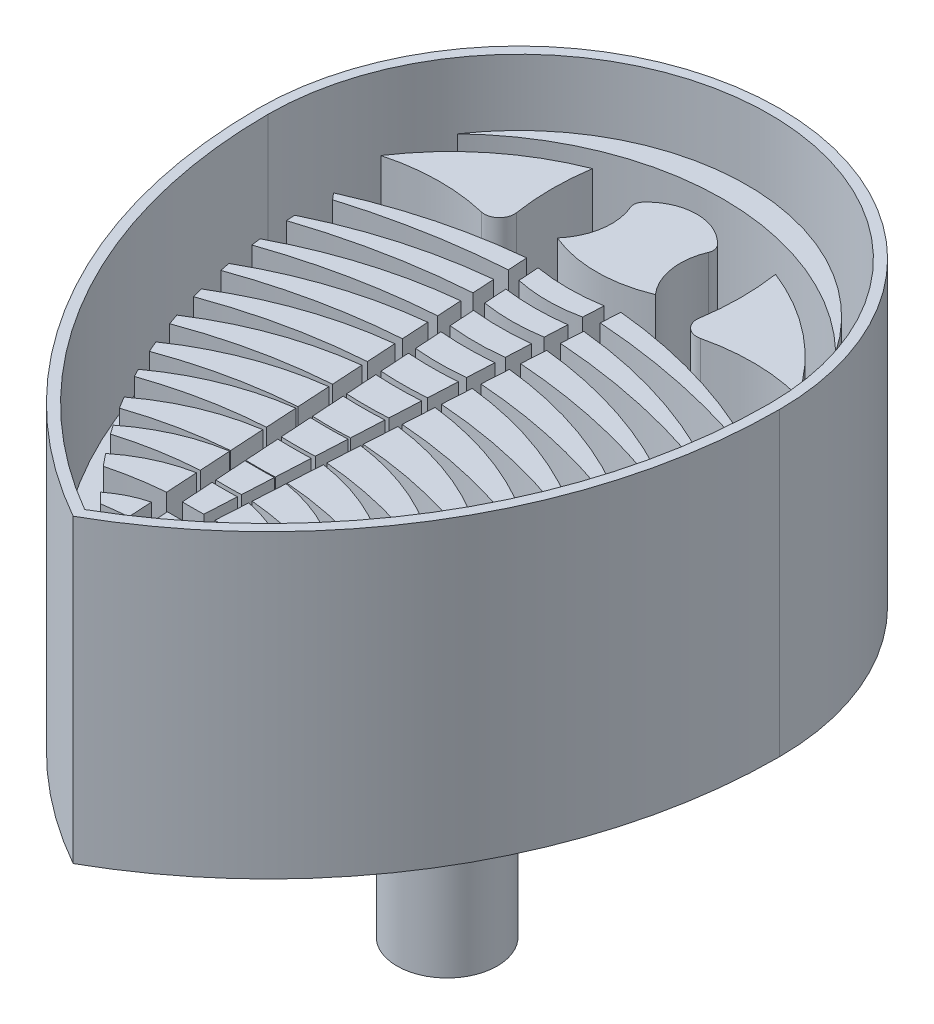
SolidWorks part; units mm, degrees
ref_plane "Přední rovina" through (0, 0, 0) normal (0, 0, 1) x (1, 0, 0)
ref_plane "Horní rovina" through (0, 0, 0) normal (0, 1, 0) x (1, 0, 0)
ref_plane "Pravá rovina" through (0, 0, 0) normal (1, 0, 0) x (0, 0, -1)
sketch "Skica1" plane through (0, 0, 0) normal (0, 1, 0) x (1, 0, 0)
  arc A0 (5, 0) -> (-5, 0) centre (0, 0) ccw
  arc A1 (-5, 0) -> (0, -8.6603) centre (5, 0) ccw
  arc A2 (0, -8.6603) -> (5, 0) centre (-5, 0) ccw
  dimension "D1" = 10
extrude "Přidat vysunutím1" add sketch "Skica1" against normal blind 3
sketch "Skica2" plane through (0, 0, 0) normal (0, 1, 0) x (1, 0, 0)
  line L0 (-0.9396, 1.0946) -> (-0.9163, 0.7054)
  line L1 (0.9396, 1.0946) -> (0.9163, 0.7054)
  line L2 (-0.4639, -6.8657) -> (-0.435, -7.3481)
  line L3 (-0.521, -5.9092) -> (-0.4831, -6.5437)
  line L4 (0.521, -5.9092) -> (0.4831, -6.5437)
  line L5 (-0.5631, -5.2058) -> (-0.5258, -5.8294)
  line L6 (-0.605, -4.5041) -> (-0.5642, -5.1865)
  line L7 (0.605, -4.5041) -> (0.5642, -5.1865)
  line L8 (0.6469, -3.8031) -> (0.6088, -4.4409)
  line L9 (-0.6469, -3.8031) -> (-0.6097, -4.4257)
  line L10 (-0.6887, -3.1028) -> (-0.6498, -3.7549)
  line L11 (0.6887, -3.1028) -> (0.6498, -3.7549)
  line L12 (0.7306, -2.4028) -> (0.6935, -3.0231)
  line L13 (-0.7306, -2.4028) -> (-0.6935, -3.0231)
  line L14 (-0.7724, -1.703) -> (-0.7376, -2.2844)
  line L15 (0.7724, -1.703) -> (0.7376, -2.2844)
  line L16 (0.8142, -1.0034) -> (0.7821, -1.5408)
  line L17 (-0.8142, -1.0034) -> (-0.7821, -1.5408)
  line L18 (-0.856, -0.304) -> (-0.8267, -0.7938)
  line L19 (0.856, -0.304) -> (0.8267, -0.7938)
  line L20 (0.8978, 0.3954) -> (0.8715, -0.0448)
  line L21 (-0.8978, 0.3954) -> (-0.8715, -0.0448)
  line L22 (0.4639, -6.8657) -> (0.434, -7.3648)
  line L23 (0.5631, -5.2058) -> (0.5249, -5.8452)
  line L24 (-0.6539, 1.0367) -> (-0.6272, 0.6279)
  line L25 (0.6621, 1.0381) -> (0.641, 0.6309)
  line L26 (-0.6089, 0.3483) -> (-0.5795, -0.1033)
  line L27 (0.6264, 0.3507) -> (0.6031, -0.0994)
  line L28 (0.5906, -0.3401) -> (0.5649, -0.8356)
  line L29 (-0.5638, -0.3429) -> (-0.5314, -0.8398)
  line L30 (0.5547, -1.0329) -> (0.5266, -1.5735)
  line L31 (-0.5186, -1.0361) -> (-0.4832, -1.5778)
  line L32 (-0.4732, -1.7307) -> (-0.4351, -2.3147)
  line L33 (0.5186, -1.7274) -> (0.4884, -2.3105)
  line L34 (-0.4279, -2.4264) -> (-0.3873, -3.0482)
  line L35 (0.4826, -2.4231) -> (0.4504, -3.0442)
  line L36 (-0.3369, -3.8204) -> (-0.2962, -4.4435)
  line L37 (0.4103, -3.8173) -> (0.378, -4.4401)
  line L38 (0.4464, -3.1197) -> (0.4126, -3.7721)
  line L39 (-0.3824, -3.123) -> (-0.3398, -3.7759)
  line L40 (0.3377, -5.2158) -> (0.3054, -5.8391)
  line L41 (-0.2456, -5.2184) -> (-0.205, -5.8419)
  line L42 (0.374, -4.5159) -> (0.3387, -5.1981)
  line L43 (-0.2913, -4.5188) -> (-0.2468, -5.2012)
  line L44 (-0.1999, -5.9198) -> (-0.1585, -6.554)
  line L45 (0.3013, -5.9174) -> (0.2685, -6.5517)
  line L46 (-0.1376, -6.874) -> (-0.1061, -7.3562)
  line L47 (0.2518, -6.8721) -> (0.2268, -7.3544)
  arc A0 (3.7723, 2.5471) -> (-3.7723, 2.5471) centre (0, 0) ccw
  arc A1 (3.7723, 2.5471) -> (-3.7723, 2.5471) centre (0, -1.3616) ccw
  arc A2 (-1.826, 3.293) -> (-4.1627, 1.4083) centre (0, -1.3616) ccw
  arc A7 (4.1627, 1.4083) -> (2.1882, 1.4375) centre (3.118, -2.4529) ccw
  arc A8 (-1.826, 3.293) -> (-1.8221, 1.7756) centre (3.118, 2.5471) ccw
  arc A9 (4.1627, 1.4083) -> (1.826, 3.293) centre (0, -1.3616) ccw
  arc A10 (1.8221, 1.7756) -> (1.826, 3.293) centre (-3.118, 2.5471) ccw
  arc A11 (-2.1882, 1.4375) -> (-1.8221, 1.7756) centre (-2.1185, 1.7293) ccw
  arc A12 (1.8221, 1.7756) -> (2.1882, 1.4375) centre (2.1185, 1.7293) ccw
  arc A13 (-2.1882, 1.4375) -> (-4.1627, 1.4083) centre (-3.118, -2.4529) ccw
  arc A15 (-0.9784, 1.7445) -> (-0.778, 3.0046) centre (-1.8819, 2.5341) ccw
  arc A16 (0.778, 3.0046) -> (0.9784, 1.7445) centre (1.8819, 2.5341) ccw
  arc A17 (-0.7425, 3.2169) -> (-0.778, 3.0046) centre (-0.594, 3.083) ccw
  arc A18 (0.778, 3.0046) -> (0.7425, 3.2169) centre (0.594, 3.083) ccw
  arc A20 (3.996, 0.288) -> (0.9396, 1.0946) centre (0, -8.6603) ccw
  arc A21 (-0.9784, 1.7445) -> (0.9784, 1.7445) centre (0, 4.0705) ccw
  arc A22 (0.7425, 3.2169) -> (-0.7425, 3.2169) centre (0, 2.5471) ccw
  arc A23 (3.989, -0.4811) -> (0.8978, 0.3954) centre (0, -8.6603) ccw
  arc A24 (3.9271, -1.2348) -> (0.856, -0.304) centre (0, -8.6603) ccw
  arc A25 (3.8134, -1.9708) -> (0.8142, -1.0034) centre (0, -8.6603) ccw
  arc A26 (3.6503, -2.6874) -> (0.7724, -1.703) centre (0, -8.6603) ccw
  arc A27 (3.4403, -3.3825) -> (0.7306, -2.4028) centre (0, -8.6603) ccw
  arc A28 (3.1856, -4.0546) -> (0.6887, -3.1028) centre (0, -8.6603) ccw
  arc A29 (2.8883, -4.702) -> (0.6469, -3.8031) centre (0, -8.6603) ccw
  arc A30 (2.5505, -5.3234) -> (0.605, -4.5041) centre (0, -8.6603) ccw
  arc A31 (2.1739, -5.9172) -> (0.5631, -5.2058) centre (0, -8.6603) ccw
  arc A32 (1.76, -6.4825) -> (0.521, -5.9092) centre (0, -8.6603) ccw
  arc A33 (1.1422, -7.2005) -> (0.4639, -6.8657) centre (0, -8.6603) ccw
  arc A34 (-4.9974, -0.2302) -> (0, -8.6603) centre (5, 0) ccw
  arc A35 (0, -8.6603) -> (4.9974, -0.2302) centre (-5, 0) ccw
  arc A36 (3.9992, 0.1259) -> (0.9163, 0.7054) centre (0, -12.6603) ccw
  arc A37 (3.9794, -0.6572) -> (0.8715, -0.0448) centre (0, -12.6603) ccw
  arc A38 (3.903, -1.4236) -> (0.8267, -0.7938) centre (0, -12.6603) ccw
  arc A39 (3.773, -2.1713) -> (0.7821, -1.5408) centre (0, -12.6603) ccw
  arc A40 (3.5921, -2.8981) -> (0.7376, -2.2844) centre (0, -12.6603) ccw
  arc A41 (3.3628, -3.6022) -> (0.6935, -3.0231) centre (0, -12.6603) ccw
  arc A42 (3.0872, -4.2819) -> (0.6498, -3.7549) centre (0, -12.6603) ccw
  arc A43 (2.7721, -4.9273) -> (0.6088, -4.4409) centre (-0.103, -12.6603) ccw
  arc A44 (2.4059, -5.5618) -> (0.5642, -5.1865) centre (0, -12.6603) ccw
  arc A45 (2.01, -6.1506) -> (0.5249, -5.8452) centre (-0.103, -12.6603) ccw
  arc A46 (1.5622, -6.7269) -> (0.4831, -6.5437) centre (0, -12.6603) ccw
  arc A47 (0.9136, -7.4357) -> (0.434, -7.3648) centre (-0.103, -12.6603) ccw
  arc A51 (0.9136, -7.4357) -> (1.1422, -7.2005) centre (-6.5, 0) ccw
  arc A52 (-0.9396, 1.0946) -> (-3.996, 0.288) centre (0, -8.6603) ccw
  arc A53 (-1.1422, -7.2005) -> (-0.9445, -7.4046) centre (6.5, 0) ccw
  arc A54 (-1.76, -6.4825) -> (-1.5622, -6.7269) centre (6.5, 0) ccw
  arc A55 (-2.1739, -5.9172) -> (-2.0475, -6.0984) centre (6.5, 0) ccw
  arc A56 (-2.5505, -5.3234) -> (-2.4059, -5.5618) centre (6.5, 0) ccw
  arc A57 (-2.8883, -4.702) -> (-2.8049, -4.8651) centre (6.5, 0) ccw
  arc A58 (-3.1856, -4.0546) -> (-3.0872, -4.2819) centre (6.5, 0) ccw
  arc A59 (-3.4403, -3.3825) -> (-3.3628, -3.6022) centre (6.5, 0) ccw
  arc A60 (-3.6503, -2.6874) -> (-3.5921, -2.8981) centre (6.5, 0) ccw
  arc A61 (-3.8134, -1.9708) -> (-3.773, -2.1713) centre (6.5, 0) ccw
  arc A62 (-3.9271, -1.2348) -> (-3.903, -1.4236) centre (6.5, 0) ccw
  arc A63 (-3.989, -0.4811) -> (-3.9794, -0.6572) centre (6.5, 0) ccw
  arc A64 (3.9992, 0.1259) -> (3.996, 0.288) centre (-6.5, 0) ccw
  arc A65 (3.9794, -0.6572) -> (3.989, -0.4811) centre (-6.5, 0) ccw
  arc A66 (3.903, -1.4236) -> (3.9271, -1.2348) centre (-6.5, 0) ccw
  arc A67 (3.773, -2.1713) -> (3.8134, -1.9708) centre (-6.5, 0) ccw
  arc A68 (3.5921, -2.8981) -> (3.6503, -2.6874) centre (-6.5, 0) ccw
  arc A69 (3.3628, -3.6022) -> (3.4403, -3.3825) centre (-6.5, 0) ccw
  arc A70 (3.0872, -4.2819) -> (3.1856, -4.0546) centre (-6.5, 0) ccw
  arc A71 (2.7721, -4.9273) -> (2.8883, -4.702) centre (-6.5, 0) ccw
  arc A72 (2.4059, -5.5618) -> (2.5505, -5.3234) centre (-6.5, 0) ccw
  arc A73 (2.01, -6.1506) -> (2.1739, -5.9172) centre (-6.5, 0) ccw
  arc A74 (1.5622, -6.7269) -> (1.76, -6.4825) centre (-6.5, 0) ccw
  arc A75 (-0.9163, 0.7054) -> (-3.9992, 0.1259) centre (0, -12.6603) ccw
  arc A76 (-0.8978, 0.3954) -> (-3.989, -0.4811) centre (0, -8.6603) ccw
  arc A77 (-0.8715, -0.0448) -> (-3.9794, -0.6572) centre (0, -12.6603) ccw
  arc A78 (-0.856, -0.304) -> (-3.9271, -1.2348) centre (0, -8.6603) ccw
  arc A79 (-0.8267, -0.7938) -> (-3.903, -1.4236) centre (0, -12.6603) ccw
  arc A80 (-0.8142, -1.0034) -> (-3.8134, -1.9708) centre (0, -8.6603) ccw
  arc A81 (-0.7821, -1.5408) -> (-3.773, -2.1713) centre (0, -12.6603) ccw
  arc A82 (-0.7724, -1.703) -> (-3.6503, -2.6874) centre (0, -8.6603) ccw
  arc A83 (-0.7376, -2.2844) -> (-3.5921, -2.8981) centre (0, -12.6603) ccw
  arc A84 (-0.7306, -2.4028) -> (-3.4403, -3.3825) centre (0, -8.6603) ccw
  arc A85 (-0.6935, -3.0231) -> (-3.3628, -3.6022) centre (0, -12.6603) ccw
  arc A86 (-0.6887, -3.1028) -> (-3.1856, -4.0546) centre (0, -8.6603) ccw
  arc A87 (-0.6498, -3.7549) -> (-3.0872, -4.2819) centre (0, -12.6603) ccw
  arc A88 (-0.6469, -3.8031) -> (-2.8883, -4.702) centre (0, -8.6603) ccw
  arc A89 (-0.6097, -4.4257) -> (-2.8049, -4.8651) centre (-0.103, -12.6603) ccw
  arc A90 (-0.605, -4.5041) -> (-2.5505, -5.3234) centre (0, -8.6603) ccw
  arc A91 (-0.5642, -5.1865) -> (-2.4059, -5.5618) centre (0, -12.6603) ccw
  arc A92 (-0.5631, -5.2058) -> (-2.1739, -5.9172) centre (0, -8.6603) ccw
  arc A93 (-0.5258, -5.8294) -> (-2.0475, -6.0984) centre (-0.103, -12.6603) ccw
  arc A94 (-0.521, -5.9092) -> (-1.76, -6.4825) centre (0, -8.6603) ccw
  arc A95 (-0.4831, -6.5437) -> (-1.5622, -6.7269) centre (0, -12.6603) ccw
  arc A96 (-0.4639, -6.8657) -> (-1.1422, -7.2005) centre (0, -8.6603) ccw
  arc A97 (-0.435, -7.3481) -> (-0.9445, -7.4046) centre (-0.103, -12.6603) ccw
  arc A98 (-3.996, 0.288) -> (-3.9992, 0.1259) centre (6.5, 0) ccw
  arc A100 (5, 0) -> (-5, 0) centre (0, 0) ccw construction
  arc A108 (-0.2913, -4.5188) -> (0.374, -4.5159) centre (0, 5) ccw
  arc A111 (-0.1376, -6.874) -> (0.2518, -6.8721) centre (0, 5) ccw
  arc A112 (-0.6539, 1.0367) -> (0.6621, 1.0381) centre (0, 5) ccw
  arc A113 (-0.5186, -1.0361) -> (0.5547, -1.0329) centre (0, 5) ccw
  arc A114 (-0.4732, -1.7307) -> (0.5186, -1.7274) centre (0, 5) ccw
  arc A115 (-0.5795, -0.1033) -> (0.6031, -0.0994) centre (0, 3.5471) ccw
  arc A116 (-0.6089, 0.3483) -> (0.6264, 0.3507) centre (0, 5) ccw
  arc A117 (-0.5638, -0.3429) -> (0.5906, -0.3401) centre (0, 5) ccw
  arc A118 (-0.4279, -2.4264) -> (0.4826, -2.4231) centre (0, 5) ccw
  arc A119 (-0.4351, -2.3147) -> (0.4884, -2.3105) centre (0, 3.5471) ccw
  arc A120 (-0.3873, -3.0482) -> (0.4504, -3.0442) centre (0, 3.5471) ccw
  arc A121 (-0.3824, -3.123) -> (0.4464, -3.1197) centre (0, 5) ccw
  arc A122 (-0.3369, -3.8204) -> (0.4103, -3.8173) centre (0, 5) ccw
  arc A123 (-0.1999, -5.9198) -> (0.3013, -5.9174) centre (0, 5) ccw
  arc A124 (-0.2456, -5.2184) -> (0.3377, -5.2158) centre (0, 5) ccw
  arc A125 (-0.1585, -6.554) -> (0.2685, -6.5517) centre (0, 3.5471) ccw
  arc A129 (-3.9876, 0.2918) -> (-3.8789, 0.163) centre (0, 3.5471) ccw
  arc A134 (-0.2468, -5.2012) -> (0.3387, -5.1981) centre (0, 3.5471) ccw
  arc A138 (-0.6272, 0.6279) -> (0.641, 0.6309) centre (0, 3.5471) ccw
  arc A139 (-0.4832, -1.5778) -> (0.5266, -1.5735) centre (0, 3.5471) ccw
  arc A140 (-0.2962, -4.4435) -> (0.378, -4.4401) centre (0, 3.5471) ccw
  arc A141 (-0.5314, -0.8398) -> (0.5649, -0.8356) centre (0, 3.5471) ccw
  arc A142 (-0.3398, -3.7759) -> (0.4126, -3.7721) centre (0, 3.5471) ccw
  arc A143 (-0.205, -5.8419) -> (0.3054, -5.8391) centre (0, 3.5471) ccw
  arc A144 (-0.1061, -7.3562) -> (0.2268, -7.3544) centre (0, 3.5471) ccw
  point P44 (0, -12.6603)
  dimension "D1" = 4
  dimension "D4" = 1.5
  dimension "D5" = 1.5
extrude "Přidat vysunutím2" add sketch "Skica2" along normal blind 2 contours A97 L2 A96 A53 | A95 L3 A94 A54 | A93 L5 A92 A55 | A91 L6 A90 A56 | A89 L9 A88 A57 | A87 L10 A86 A58 | A85 L13 A84 A59 | A83 L14 A82 A60 | A81 L17 A80 A61 | A77 L21 A76 A63 | A52 A129 A75 L0 | A13 A11 A8 A2 | A1 A0 | A18 A22 A17 A15 A21 A16 | A10 A12 A7 A9 | L24 A138 L25 A112 | A116 L26 A115 L27 | L29 A141 L28 A117 | L31 A139 L30 A113 | L32 A119 L33 A114 | L34 A120 L35 A118 | L39 A142 L38 A121 | L36 A140 L37 A122 | L43 A134 L42 A108 | L41 A143 L40 A124 | L44 A125 L45 A123 | L46 A144 L47 A111 | A47 A51 A33 L22 | A46 A74 A32 L4 | A45 A73 A31 L23 | A44 A72 A30 L7 | A43 A71 A29 L8 | A42 A70 A28 L11 | A41 A69 A27 L12 | A40 A68 A26 L15 | A39 A67 A25 L16 | A38 A66 A24 L19 | A37 A65 A23 L20 | A84 A59 A85 L13 | A78 A62 A79 L18 | A36 L1 A20 A64 region at (-2.2521, 0, -0.6787) region at (-0.7289, 0, 7.169) region at (-1.0328, 0, 6.351) region at (1.0328, 0, 6.351) region at (-1.2291, 0, 5.6712) region at (-1.4297, 0, 5.0378) region at (1.4297, 0, 5.0378) region at (1.6079, 0, 4.3464) region at (-1.5774, 0, 4.3173) region at (-1.7578, 0, 3.6642) region at (1.7578, 0, 3.6642) region at (1.8946, 0, 2.9605) region at (-1.8946, 0, 2.9605) region at (-2.0121, 0, 2.2477) region at (2.0121, 0, 2.2477) region at (2.1095, 0, 1.527) region at (-2.1095, 0, 1.527) region at (2.1859, 0, 0.7993) region at (2.2402, 0, 0.0656) region at (-2.2402, 0, 0.0656) region at (0.728, 0, 7.1802) region at (1.2436, 0, 5.6936) region at (0.0053, 0, -0.7937) region at (0.0101, 0, -0.0961) region at (0.0149, 0, 0.6092) region at (0.0198, 0, 1.3186) region at (0.0246, 0, 2.0295) region at (0.0294, 0, 2.7402) region at (0.0387, 0, 4.13) region at (0.0341, 0, 3.4492) region at (0.0481, 0, 5.5244) region at (0.0436, 0, 4.8548) region at (0.0528, 0, 6.229) region at (0.0587, 0, 7.1089) region at (0, 0, -4.1486) region at (-2.6742, 0, -2.1513) region at (2.6742, 0, -2.1513) region at (0, 0, -2.4956)
extrude "Vysunout tenkostěnný1" add sketch "Skica1<2>" along normal mid plane 6 separate body thin thin type one direction wall 0.2
sketch "Skica1<2>" plane through (0, 0, 0) normal (0, 1, 0) x (1, 0, 0) same geometry as "Skica1"
ref_plane "Rovina1" through (0, -3, 0) normal (0, -1, 0) x (-1, 0, 0)
sketch "Skica4" plane through (0, -3, 0) normal (0, -1, 0) x (-1, 0, 0)
  circle A0 centre (0, -1.4317) radius 1
  dimension "D1" = 2
extrude "Přidat vysunutím3" add sketch "Skica4" along normal blind 5
ref_plane "Rovina2" through (0, -8, 0) normal (0, -1, 0) x (-1, 0, 0)
sketch "Skica5" plane through (0, -8, 0) normal (0, -1, 0) x (-1, 0, 0)
  circle A0 centre (0, -1.4317) radius 3
  dimension "D1" = 6
scale "Měřítko2" scale about origin uniform scaling yes scale factor 10
